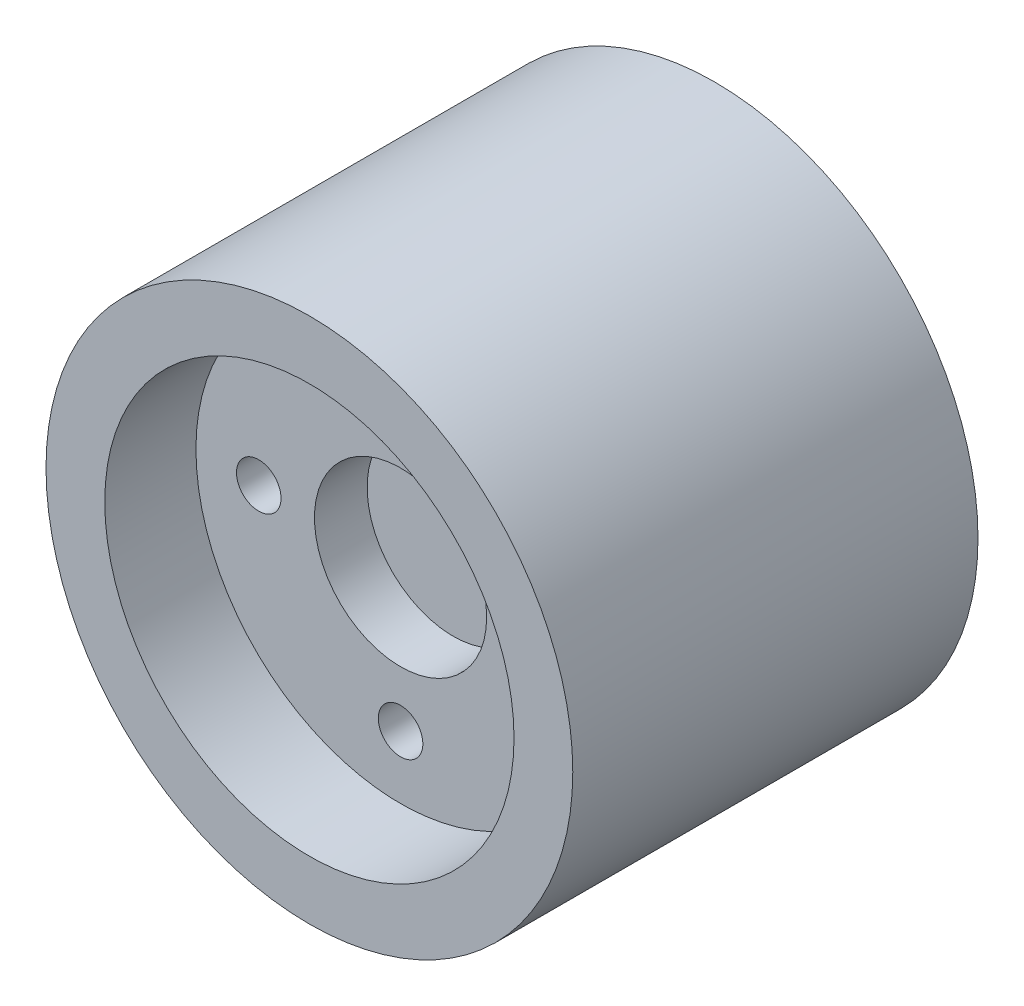
SolidWorks part; units mm, degrees
ref_plane "Front Plane" through (0, 0, 0) normal (0, 0, 1) x (1, 0, 0)
ref_plane "Top Plane" through (0, 0, 0) normal (0, 1, 0) x (1, 0, 0)
ref_plane "Right Plane" through (0, 0, 0) normal (1, 0, 0) x (0, 0, -1)
sketch "Sketch1" plane through (0, 0, 0) normal (0, 0, 1) x (1, 0, 0)
  circle A0 centre (0, 0) radius 13
  dimension "D1" = 26
extrude "Boss-Extrude1" add sketch "Sketch1" along normal blind 20
sketch "Sketch2" plane through (0, 0, 20) normal (0, 0, 1) x (1, 0, 0)
  circle A0 centre (0, 0) radius 10.1
  dimension "D1" = 20.2
extrude "Cut-Extrude1" cut sketch "Sketch2" against normal blind 4.5
sketch "Sketch3" plane through (0, 0, 15.5) normal (0, 0, 1) x (1, 0, 0)
  circle A0 centre (0, 0) radius 4.25
  dimension "D1" = 8.5
extrude "Cut-Extrude2" cut sketch "Sketch3" against normal blind 2.6
sketch "Sketch4" plane through (0, 0, 0) normal (0, 0, -1) x (-1, 0, 0)
  circle A0 centre (0, 0) radius 2.125
  dimension "D1" = 4.25
extrude "Cut-Extrude3" cut sketch "Sketch4" against normal blind 10
sketch "Sketch5" plane through (0, 0, 0) normal (0, 0, -1) x (-1, 0, 0)
  circle A0 centre (0, 7) radius 2
  circle A1 centre (7, 0) radius 2
  circle A2 centre (0, -7) radius 2
  circle A4 centre (-7, 0) radius 2 [skipped]
  circle A5 centre (0, 0) radius 2.125 construction
  point P4 (0, 0)
  point P5 (0, 0)
  point P11 (0, 0)
  dimension "D2" = 4
  dimension "D1" = 7
  dimension "D4" = 7
extrude "Cut-Extrude4" cut sketch "Sketch5" against normal offset from surface (13.5 mm away) 2 up to face at (4.25, 0, 15.5)
sketch "Sketch6" plane through (0, 0, 0) normal (0, 0, -1) x (-1, 0, 0)
  circle A0 centre (0, 7) radius 1.1
  circle A1 centre (7, 0) radius 1.1
  circle A2 centre (0, -7) radius 1.1
  circle A4 centre (-7, 0) radius 1.1 [skipped]
  circle A5 centre (0, 7) radius 2 construction
  point P5 (0, 0)
  point P10 (0, 0)
  point P11 (0, 0)
  point P12 (0, 0)
  point P15 (0, 0)
  point P16 (0, 0)
  dimension "D1" = 2.2
  dimension "D2" = 7
  dimension "D4" = 7
extrude "Cut-Extrude5" cut sketch "Sketch6" against normal through all
sketch "Sketch7" plane through (0, 0, 0) normal (0, 0, -1) x (-1, 0, 0)
  line L0 (0, 0) -> (-20.2439, 0) construction
  circle A0 centre (-6, 5) radius 2.1
  circle A1 centre (-6, -5) radius 2.1
  dimension "D3" = 4.2
  dimension "D1" = 5
  dimension "D2" = 6
extrude "Cut-Extrude6" cut sketch "Sketch7" against normal blind 6
equation "\"L1\"= 120mm'Upper arm"
equation "\"L3\"= 75mm'Wrist→TCP"
equation "\"h0\"= 75mm'Shoulder height"
equation "\"t_link\"= 3mm'Link plate thickness"
equation "\"t_bracket\"= 4mm'Bracket thickness"
equation "\"d_pin\"= 4mm'Pin diameter (M4)"
equation "\"c_fit\"= 0.2mm'Nominal clearance - measured PLA 2026-10-01"
equation "\"L2\"= 120mm'Forearm"
equation "\"c_fit_pivot\"= \"c_fit\" + 0.05mm'Gripper pivot clearance - chosen 0.25 mm 2026-10-01"
equation "\"d_pin_gripper\"= 3mm'Gripper pivot diameter"
equation "\"w_link\"= 20mm'Link plate depth (bending direction)"
equation "\"w_gap\"= 20mm'Twin-plate gap - provisional, set by elbow servo mount"
equation "\"d_boss\"= 13mm'MG996R output boss dia - from downloaded model, verify with calipers"
equation "\"c_boss\"= 1mm'Radial clearance around servo boss"
equation "\"d_servo_hole\"= \"d_boss\" + 2 * \"c_boss\"'Plate clearance hole for servo boss (15 mm)"
equation "\"t_rim\"= 9.5mm'Min material around servo hole (M3 hole + 3 mm webs each side)"
equation "\"w_link_end\"= \"d_servo_hole\" + 2 * \"t_rim\"'Link plate end width at servo end (34 mm)"
equation "\"d_hole_m3\"= \"d_pin_gripper\" + \"c_fit\"'M3 bolt clearance hole (spacer and adapter bolts)"
equation "\"d_hole_pivot\"= \"d_pin\" + \"c_fit_pivot\"'M4 pivot hole where the pin rotates (4.25 mm)"
equation "\"d_horn\"= 20mm'Horn disc diameter (circular horn) - from MG996R model"
equation "\"t_horn\"= 2.3mm'Horn disc thickness"
equation "\"g_horn\"= 2.2mm'Gap from horn disc to plate 2 inner face - from MockShoulder"
equation "\"d_horn_pocket\"= \"d_horn\" + \"c_fit\"'Adapter pocket for horn disc (20.2 mm)"
equation "\"h_horn_pocket\"= \"g_horn\" + \"t_horn\"'Pocket depth from adapter plate-2 face (4.5 mm)"
equation "\"d_horn_screw_cb\"= 8.5mm'Recess for horn centre-screw head (head is 7.5 mm)"
equation "\"h_horn_screw_cb\"= 2.6mm'Recess depth (head is 2.35 mm tall)"
equation "\"d_adapter\"= 26mm'Horn adapter outer diameter"
equation "\"h_adapter\"= \"w_gap\"'Adapter length, fills the plate gap"
equation "\"t_adapter_floor\"= 2mm'Floor under horn disc that the horn screws pass through"
equation "\"d_horn_screw_hole\"= 2.2mm'Clearance for M2 self-tapper through the floor"
equation "\"r_horn_screw\"= 7mm'Horn screw hole radius (14 mm square pattern)"
equation "\"d_access\"= 4mm'Access bore for the M2 screws from the plate-1 side"
equation "\"d_insert_m3\"= 4.2mm'Hole for M3 heat-set insert - check the insert maker spec"
equation "\"h_insert_m3\"= 6mm'Insert hole depth"
equation "\"x_adapter_bolt\"= 6mm'Adapter bolt offset from pin, along the arm toward its middle"
equation "\"y_adapter_bolt\"= 5mm'Adapter bolt offset from pin, across the arm (+/-)"
equation "\"d_csk_m3\"= 6.4mm'Countersink diameter in plate 1 for M3 flat head (90 deg)"
equation "\"h_pin_bore\"= 10mm'M4 pin engagement depth in the adapter"
equation "\"D1@Sketch1\"=\"d_adapter\""
equation "\"D1@Boss-Extrude1\"=\"w_gap\""
equation "\"D1@Sketch2\"=\"d_horn_pocket\""
equation "\"D1@Sketch3\"=\"d_horn_screw_cb\""
equation "\"D1@Cut-Extrude2\"=\"h_horn_screw_cb\""
equation "\"D1@Sketch4\"=\"d_hole_pivot\""
equation "\"D1@Cut-Extrude3\"=\"h_pin_bore\""
equation "\"D1@Sketch5\"=\"r_horn_screw\""
equation "\"D2@Sketch5\"=\"d_access\""
equation "\"D4@Sketch5\"=\"r_horn_screw\""
equation "\"D1@Cut-Extrude4\"=\"t_adapter_floor\""
equation "\"D1@Sketch6\"=\"d_horn_screw_hole\""
equation "\"D2@Sketch6\"=\"r_horn_screw\""
equation "\"D4@Sketch6\"=\"r_horn_screw\""
equation "\"D1@Sketch7\"=\"y_adapter_bolt\""
equation "\"D2@Sketch7\"=\"x_adapter_bolt\""
equation "\"D3@Sketch7\"=\"d_insert_m3\""
equation "\"D1@Cut-Extrude6\"=\"h_insert_m3\""
